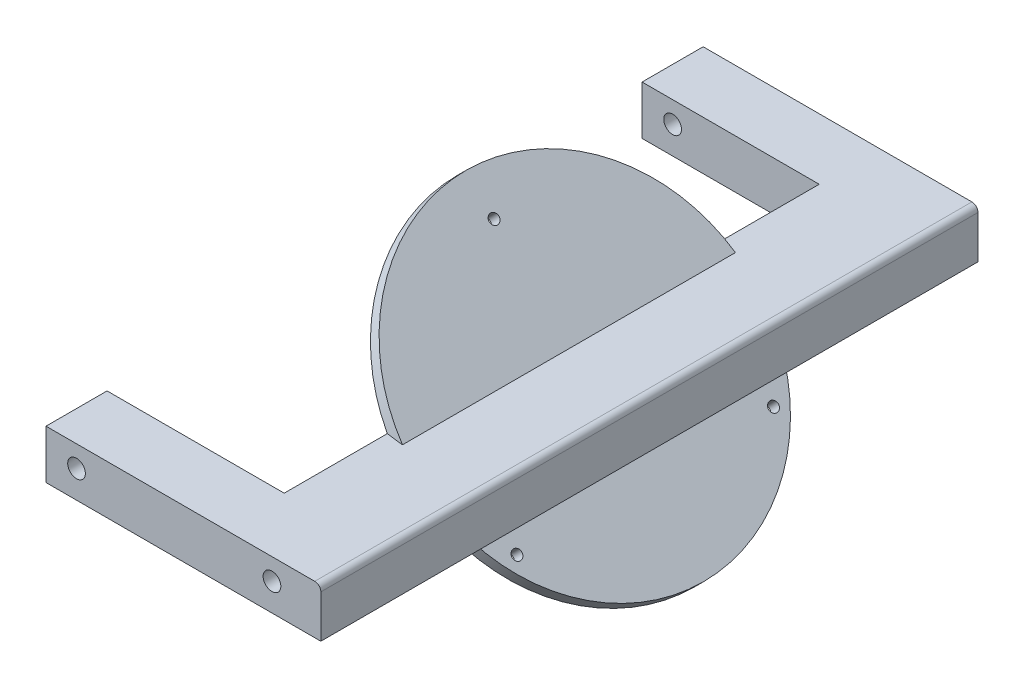
SolidWorks part; units mm, degrees
material "Nylon 101"
ref_plane "Front Plane" through (0, 0, 0) normal (0, 0, 1) x (1, 0, 0)
ref_plane "Top Plane" through (0, 0, 0) normal (0, 1, 0) x (1, 0, 0)
ref_plane "Right Plane" through (0, 0, 0) normal (1, 0, 0) x (0, 0, -1)
sketch "Sketch1" plane through (0, 0, 0) normal (0, 0, 1) x (1, 0, 0)
  line L4 (8, 4) -> (-8, 4)
  line L6 (0, -4) -> (-8, 4)
  line L7 (0, 4) -> (0, -4) construction
  line L8 (8, 4) -> (8, -4)
  line L9 (8, -4) -> (0, -4)
  dimension "D1" = 8
  dimension "D2" = 45
extrude "Base" add sketch "Sketch1" along normal mid plane 107.6
sketch "Sketch4" plane through (-2, -2, 0) normal (-0.7071, -0.7071, 0) x (0, 0, 1)
  line L0 (-53.8, 2.8284) -> (53.8, 2.8284) construction
  line L1 (-53.8, 8.4853) -> (-53.8, -2.8284) construction
  line L2 (53.8, 8.4853) -> (53.8, -2.8284) construction
  line L3 (0, 8.4853) -> (0, -2.8284) construction
  line L4 (53.8, 8.4853) -> (-53.8, 8.4853) construction
  line L6 (53.8, -2.8284) -> (-53.8, -2.8284) construction
  line L7 (-17.5, 20.3284) -> (17.5, 20.3284)
  line L8 (-17.5, 20.3284) -> (-17.5, -14.6716)
  line L9 (-17.5, -14.6716) -> (17.5, -14.6716)
  line L10 (17.5, 20.3284) -> (17.5, -14.6716)
  line L11 (-17.5, 20.3284) -> (17.5, -14.6716) construction
  line L12 (-17.5, -14.6716) -> (17.5, 20.3284) construction
  circle A0 centre (0, 2.8284) radius 27.5
  point P16 (0, 2.8284)
  point P17 (0, 2.8284)
  line M5 (53.8, 8.4853) -> (-53.8, 8.4853)
  dimension "D1" = 55
  dimension "D2" = 35
extrude "Boss-Extrude2" add sketch "Sketch4" against normal blind 2 contours A0 L8 L7 L10 M5 | L10 L7 L8 M5 | A0 L10 L9 L8 | A0 L8 M5 | L10 L8 L9 | L10 L8 M5 | A0 L10 M5 region at (-16.475, 12.475, 0) region at (-12.1872, 8.1872, 0) region at (0.1872, -4.1872, 0) region at (0.1872, -4.1872, -18.1422)
hole_wizard "M2x0.4 Tapped Hole1" positions "Sketch5" profile "Sketch6" tap size "M2x0.4" standard "ANSI Metric" end condition through all
sketch "Sketch5" plane through (-0.5858, -0.5858, 0) normal (0.7071, 0.7071, 0) x (0.7071, -0.7071, 0)
  line L4 (-8.4853, 0) -> (2.8284, 0) construction
  line L5 (-20.3284, 17.5) -> (-20.3284, -17.5) construction
  line L6 (-20.3284, -17.5) -> (14.6716, -17.5) construction
  line L7 (14.6716, 17.5) -> (14.6716, -17.5) construction
  line L8 (-20.3284, 17.5) -> (14.6716, 17.5) construction
  point P0 (-23.8284, 0)
  point P2 (11.1716, 21)
  point P4 (11.1716, -21)
  dimension "D1" = 3.5
  dimension "D2" = 3.5
  dimension "D3" = 3.5
  dimension "D4" = 3.5
sketch "Sketch6" plane through (-17.435, 16.2635, 0) normal (0, 0, 1) x (-0.7071, 0.7071, 0)
  line L0 (0, 0) -> (0, 29.5)
  line L1 (0, 29.5) -> (0.8, 29.5)
  line L2 (0.8, 29.5) -> (0.8, 0)
  line L5 (0.8, 0) -> (0, 0)
  line L11 (0, -6.35) -> (0, 107.95) construction
  dimension "Thru Tap Drill Dia." = 1.6
  dimension "Thru Tap Drill Depth" = 29.5
cosmetic thread "Hole Thread1" parameters "D2"=2
cosmetic thread "Hole Thread2" parameters "D2"=2
cosmetic thread "Hole Thread3" parameters "D2"=2
ref_plane "Plane1" through (-2, 2, 0) normal (0.7071, -0.7071, 0) x (0, 0, 1)
sketch "Sketch8" plane through (-2, 2, 0) normal (0.7071, -0.7071, 0) x (0, 0, 1)
  line L0 (0, 3.8284) -> (0, 2.8284)
  line L1 (27.5, 2.8284) -> (-27.5, 2.8284) construction
  line L2 (0, 2.8284) -> (-12, 2.8284)
  line L4 (0, 2.8284) -> (0, 10.3284) construction
  line L5 (-6.5, 10.3284) -> (-12, 2.8284)
  arc A1 (-6.5, 10.3284) -> (0, 3.8284) centre (0, 10.3284) ccw
  dimension "D2" = 6.5
  dimension "D1" = 1
  dimension "D3" = 12
revolve "Revolve1" add sketch "Sketch8" angle 360 about L4
fillet "Fillet1" radius 0.5 1 edges at (-13.8995, -0.7071, 0)
hole_wizard "Side Holes" positions "Sketch2" profile "Sketch3" hole size "M2.5" standard "ANSI Metric" end condition through all
sketch "Sketch2" plane through (0, 0, 53.8) normal (0, 0, 1) x (1, 0, 0)
  line L0 (0, 0.5) -> (0, 4) construction
  line L1 (8, 4) -> (-8, 4) construction
  line L3 (-4.5, 0.5) -> (8, 0.5) construction
  line L4 (-8, 4) -> (0, -4) construction
  line L6 (8, -4) -> (8, 4) construction
  point P0 (0, 0.5)
  dimension "D1" = 3.5
sketch "Sketch3" plane through (0, 0.5, 53.8) normal (1, 0, 0) x (0, -1, 0)
  line L0 (0, 0) -> (0, 107.6)
  line L1 (0, 107.6) -> (1.45, 107.6)
  line L2 (1.45, 107.6) -> (1.45, 0)
  line L5 (1.45, 0) -> (0, 0)
  line L11 (0, -6.35) -> (0, 107.95) construction
  dimension "Thru Hole Dia." = 2.9
  dimension "Thru Hole Depth" = 107.6
sketch "Sketch9" plane through (0, 0, 53.8) normal (0, 0, 1) x (1, 0, 0)
  line L0 (-8, 4) -> (0, -4)
  line L1 (0, -4) -> (-37, -4)
  line L2 (-37, -4) -> (-37, 4)
  line L3 (-37, 4) -> (-8, 4)
  line L4 (8, -4) -> (8, 4) construction
  dimension "D1" = 45
extrude "Side Arm" add sketch "Sketch9" against normal blind 10
mirror "Mirror1" about plane through (0, 0, 0) normal (0, 0, 1) of "Side Arm"
hole_wizard "M2.5 Clearance Hole1" positions "Sketch10" profile "Sketch11" hole size "M2.5" standard "ANSI Metric" end condition through all
sketch "Sketch10" plane through (0, 0, 53.8) normal (0, 0, 1) x (1, 0, 0)
  line L0 (-37, 4) -> (-37, -4) construction
  point P0 (-32, 0.5)
  dimension "D1" = 5
sketch "Sketch11" plane through (-32, 0.5, 53.8) normal (1, 0, 0) x (0, -1, 0)
  line L0 (0, 0) -> (0, 107.6)
  line L1 (0, 107.6) -> (1.45, 107.6)
  line L2 (1.45, 107.6) -> (1.45, 0)
  line L5 (1.45, 0) -> (0, 0)
  line L11 (0, -6.35) -> (0, 107.95) construction
  dimension "Thru Hole Dia." = 2.9
  dimension "Thru Hole Depth" = 107.6
fillet "Fillet2" radius 1 1 edges at (8, 4, 0)
